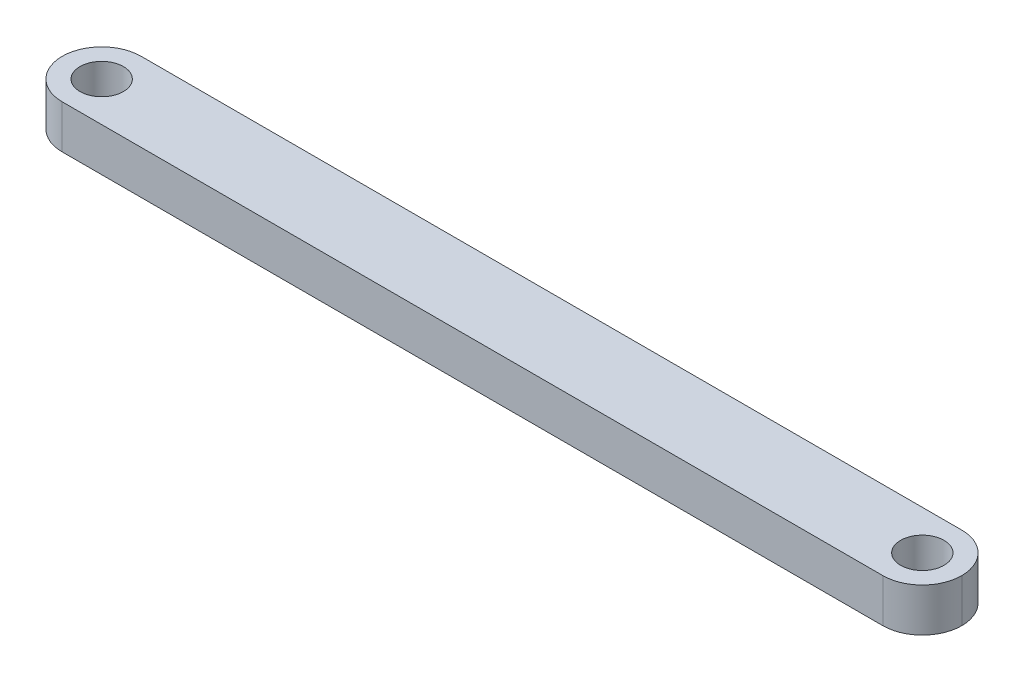
SolidWorks part; units mm, degrees
ref_plane "Front Plane" through (0, 0, 0) normal (0, 0, 1) x (1, 0, 0)
ref_plane "Top Plane" through (0, 0, 0) normal (0, 1, 0) x (1, 0, 0)
ref_plane "Right Plane" through (0, 0, 0) normal (1, 0, 0) x (0, 0, -1)
sketch "Sketch1" plane through (0, 0, 0) normal (0, 1, 0) x (1, 0, 0)
  line L0 (-66.04, 0) -> (0, 0) construction
  line L1 (-72.39, -6.35) -> (72.39, -6.35) construction
  line L2 (-72.39, -6.35) -> (-72.39, 6.35)
  line L3 (-72.39, 6.35) -> (72.39, 6.35)
  line L4 (72.39, -6.35) -> (72.39, 6.35)
  line L5 (-72.39, -6.35) -> (72.39, 6.35) construction
  line L6 (-72.39, 6.35) -> (72.39, -6.35) construction
  line L7 (0, 6.35) -> (0, -6.35) construction
  line L8 (-6.35, -31.75) -> (-6.35, 6.35) construction
  line L9 (-6.35, -31.75) -> (6.35, -31.75)
  line L10 (-6.35, 6.35) -> (6.35, 6.35)
  line L11 (6.35, -31.75) -> (6.35, 6.35) construction
  line L12 (-6.35, -31.75) -> (6.35, 6.35) construction
  line L13 (-6.35, 6.35) -> (6.35, -31.75) construction
  line L14 (-72.39, -6.35) -> (-6.35, -6.35)
  line L15 (-6.35, -6.35) -> (-6.35, -31.75)
  line L16 (6.35, -31.75) -> (6.35, -6.35)
  line L17 (6.35, -6.35) -> (72.39, -6.35)
  line L18 (-6.35, -6.35) -> (6.35, -6.35)
  circle A0 centre (-66.04, 0) radius 3.4925
  circle A1 centre (66.04, 0) radius 3.4925
  circle A2 centre (0, -25.4) radius 3.4925
  point P0 (0, 0)
  point P13 (0, -12.7)
  point P22 (0, -31.75)
  dimension "D5" = 12.7
  dimension "D6" = 38.1
  dimension "D3" = 6.35
  dimension "D4" = 6.985
  dimension "D7" = 6.35
  dimension "D1" = 144.78
  dimension "D2" = 12.7
extrude "Boss-Extrude1" add sketch "Sketch1" along normal blind 6.985 contours L16 L17 L4 L3 L2 L14 L15 L9 A2 A0 A1 region at (0, 0, 0)
fillet "Fillet1" radius 6.35 4 edges at (72.39, 3.4925, -6.35) (-72.39, 3.4925, -6.35) (-72.39, 3.4925, 6.35) (72.39, 3.4925, 6.35)
